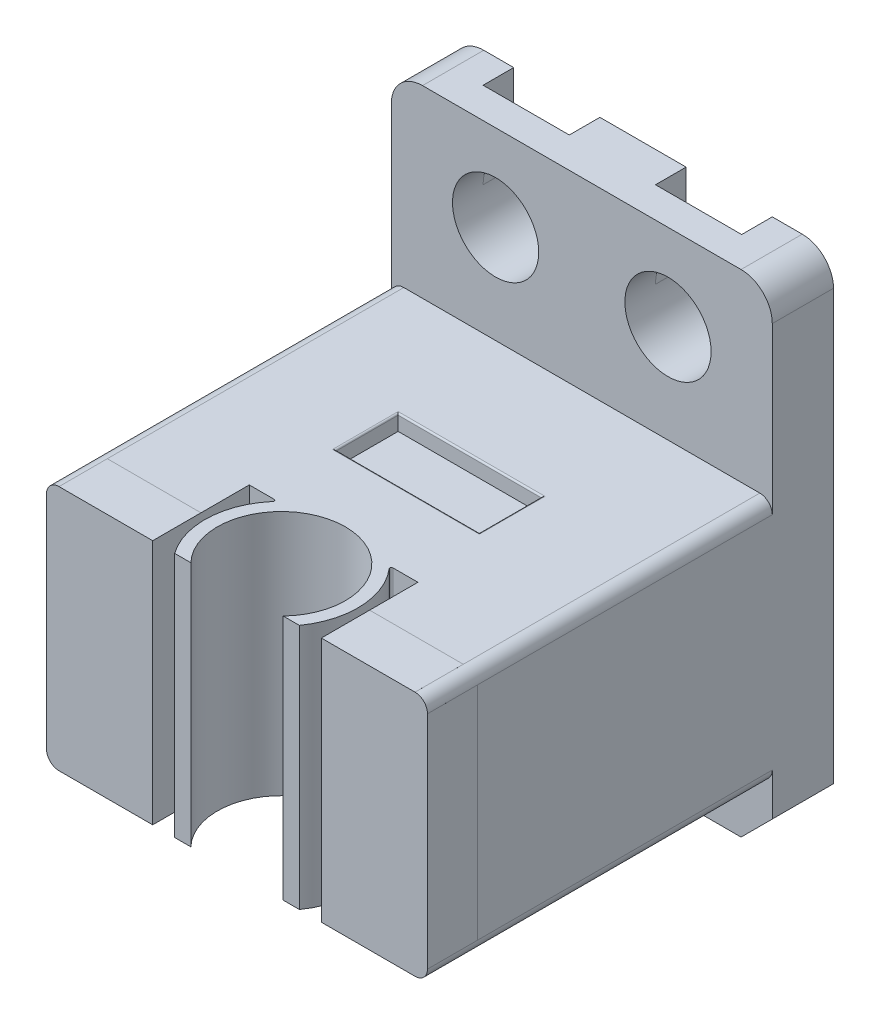
SolidWorks part; units mm, degrees
ref_plane "Front Plane" through (0, 0, 0) normal (0, 0, 1) x (1, 0, 0)
ref_plane "Top Plane" through (0, 0, 0) normal (0, 1, 0) x (1, 0, 0)
ref_plane "Right Plane" through (0, 0, 0) normal (1, 0, 0) x (0, 0, -1)
sketch "Sketch2" plane through (0, 0, 0) normal (0, 0, 1) x (1, 0, 0)
  line L0 (-5.2578, 6.4897) -> (-1.4809, 6.4897) construction
  line L1 (-6.477, 9.9949) -> (6.477, 9.9949)
  line L2 (-7.747, 8.7249) -> (-7.747, -9.9949)
  line L3 (-7.747, -9.9949) -> (7.747, -9.9949)
  line L4 (7.747, 8.7249) -> (7.747, -9.9949)
  line L5 (-7.747, 9.9949) -> (7.747, -9.9949) construction
  line L6 (-7.747, -9.9949) -> (7.747, 9.9949) construction
  line L7 (0, -9.9949) -> (0, 19.523) construction
  circle A0 centre (-3.5052, 6.4897) radius 1.7526
  circle A1 centre (3.5052, 6.4897) radius 1.7526
  arc A2 (6.477, 9.9949) -> (7.747, 8.7249) centre (6.477, 8.7249) cw
  arc A3 (-6.477, 9.9949) -> (-7.747, 8.7249) centre (-6.477, 8.7249) ccw
  point P0 (0, 0)
  dimension "D3" = 7.0104
  dimension "D4" = 3.5052
  dimension "D5" = 3.5052
  dimension "D6" = 3.5052
  dimension "D8" = 1.27
  dimension "D1" = 15.494
  dimension "D2" = 19.9898
  dimension "D7" = 3.5052
extrude "Boss-Extrude1" add sketch "Sketch2" along normal blind 2.4892
sketch "Sketch3" plane through (0, 0, 2.4892) normal (0, 0, 1) x (1, 0, 0)
  line L0 (7.747, -9.9949) -> (7.747, 8.7249) construction
  line L1 (0, 16.793) -> (0, -17.5216) construction
  line L2 (-13.8424, -2.5019) -> (21.1306, -2.5019) construction
  line L4 (-5.2578, 6.4897) -> (11.8832, 6.4897) construction
  line L5 (-7.239, 2.5019) -> (7.239, 2.5019)
  line L6 (-7.747, 1.9939) -> (-7.747, -6.9977)
  line L7 (-7.239, -7.5057) -> (7.239, -7.5057)
  line L8 (7.747, 1.9939) -> (7.747, -6.9977)
  line L9 (-7.747, 2.5019) -> (7.747, -7.5057) construction
  line L10 (-7.747, -7.5057) -> (7.747, 2.5019) construction
  circle A0 centre (-3.5052, 6.4897) radius 1.7526 construction
  arc A1 (7.239, 2.5019) -> (7.747, 1.9939) centre (7.239, 1.9939) cw
  arc A2 (7.239, -7.5057) -> (7.747, -6.9977) centre (7.239, -6.9977) ccw
  arc A3 (-7.747, -6.9977) -> (-7.239, -7.5057) centre (-7.239, -6.9977) ccw
  arc A4 (-7.239, 2.5019) -> (-7.747, 1.9939) centre (-7.239, 1.9939) ccw
  point P0 (0, -2.5019)
  dimension "D3" = 0.508
  dimension "D1" = 8.9916
  dimension "D2" = 10.0076
extrude "Boss-Extrude2" add sketch "Sketch3" along normal blind 14.0208
sketch "Sketch4" plane through (0, -7.5057, 0) normal (0, -1, 0) x (1, 0, 0)
  line L0 (0, -1.7528) -> (0, 17.6382) construction
  line L1 (-9.4019, 8.3058) -> (11.8673, 8.3058) construction
  line L2 (-3.429, 12.5824) -> (-2.413, 12.5824)
  line L3 (-19.205, 14.7066) -> (19.1548, 14.7066) construction
  line L4 (-7.747, 0) -> (7.747, 0) construction
  line L5 (-3.429, 16.51) -> (-2.5356, 16.51)
  line L10 (-7.239, 16.51) -> (7.239, 16.51) construction
  line L11 (-3.429, 16.51) -> (-3.429, 12.5824)
  line L12 (3.429, 16.51) -> (3.429, 12.5824)
  line L13 (3.429, 16.51) -> (2.5356, 16.51)
  line L14 (3.429, 12.5824) -> (2.413, 12.5824)
  circle A0 centre (0, 14.7066) radius 2.6035
  arc A1 (2.3656, 12.6853) -> (2.5356, 16.51) centre (0, 14.7066) ccw
  arc A2 (-2.413, 12.5824) -> (-2.3656, 12.6853) centre (-2.413, 12.6448) ccw
  arc A3 (2.413, 12.5824) -> (2.3656, 12.6853) centre (2.413, 12.6448) cw
  arc A4 (-2.5356, 16.51) -> (-2.3656, 12.6853) centre (0, 14.7066) ccw
  point P12 (0, 8.3058)
  dimension "D3" = 5.207
  dimension "D4" = 0.508
  dimension "D5" = 0.0624
  dimension "D1" = 14.7066
  dimension "D2" = 8.3058
  dimension "D6" = 6.858
  dimension "D7" = 1.016
extrude "Cut-Extrude3" cut sketch "Sketch4" against normal through all
sketch "Sketch5" plane through (0, 2.5019, 0) normal (0, 1, 0) x (1, 0, 0)
  line L0 (10.9012, -8.3058) -> (-14.0254, -8.3058) construction
  line L1 (0, 0) -> (0, -20.817) construction
  line L2 (6.477, 0) -> (-6.477, 0) construction
  line L3 (3.429, -12.5824) -> (3.429, -16.51) construction
  line L4 (2.921, -9.5758) -> (-2.921, -9.5758)
  line L5 (2.921, -9.5758) -> (2.921, -7.0358)
  line L6 (2.921, -7.0358) -> (-2.921, -7.0358)
  line L7 (-2.921, -9.5758) -> (-2.921, -7.0358)
  line L8 (2.921, -9.5758) -> (-2.921, -7.0358) construction
  line L9 (2.921, -7.0358) -> (-2.921, -9.5758) construction
  point P8 (0, -8.3058)
  dimension "D1" = 8.3058
  dimension "D2" = 2.54
  dimension "D3" = 0.508
extrude "Cut-Extrude4" cut sketch "Sketch5" against normal blind 0.635
fillet "Fillet1" radius 0.0648 4 edges at (-2.921, 2.5019, 8.3058) (0, 2.5019, 7.0358) (2.921, 2.5019, 8.3058) (0, 2.5019, 9.5758)
sketch "Sketch6" plane through (0, -9.9949, 0) normal (0, -1, 0) x (1, 0, 0)
  line L0 (-10.0705, 5.9776) -> (12.9955, 5.9776) construction
  line L1 (0, -2.2125) -> (0, 17.7614) construction
  line L3 (-7.747, 0) -> (7.747, 0) construction
  circle A0 centre (0, 2.9972) radius 2.6035
  dimension "D1" = 5.207
  dimension "D2" = 2.9972
extrude "Boss-Extrude3" add sketch "Sketch6" against normal up to next and the other way blind 1.27
sketch "Sketch7" plane through (0, -11.2649, 0) normal (0, -1, 0) x (1, 0, 0)
  circle A0 centre (0, 2.9972) radius 2.3495
  circle A1 centre (0, 2.9972) radius 2.6035 construction
  dimension "D1" = 0.254
extrude "Boss-Extrude4" add sketch "Sketch7" along normal blind 0.7366
fillet "Fillet2" radius 0.127 1 edges at (0, -11.2649, 0.6477)
sketch "Sketch8" plane through (0, 9.9949, 0) normal (0, 1, 0) x (1, 0, 0)
  line L0 (9.0247, -1.2446) -> (-10.9399, -1.2446) construction
  line L1 (6.477, -2.4892) -> (-6.477, -2.4892) construction
  line L2 (6.477, 0) -> (-6.477, 0) construction
  line L3 (0, -5.7739) -> (0, 1.6257) construction
  line L4 (5.2578, 0) -> (1.7526, 0)
  line L5 (5.2578, 0) -> (5.2578, -1.2446)
  line L6 (5.2578, -1.2446) -> (1.7526, -1.2446)
  line L7 (1.7526, 0) -> (1.7526, -1.2446)
  line L8 (-1.7526, 0) -> (-5.2578, 0)
  line L9 (-1.7526, 0) -> (-1.7526, -1.2446)
  line L10 (-1.7526, -1.2446) -> (-5.2578, -1.2446)
  line L11 (-5.2578, 0) -> (-5.2578, -1.2446)
  line L12 (3.5052, -1.2446) -> (3.5052, 0) construction
  line L13 (-3.5052, -1.2446) -> (-3.5052, 0) construction
  dimension "D1" = 3.5052
  dimension "D2" = 3.5052
  dimension "D3" = 7.0104
  dimension "D4" = 3.5052
extrude "Cut-Extrude5" cut sketch "Sketch8" against normal blind 3.5052
chamfer "Chamfer1" distance 1.27 angle 45 2 edges at (-7.747, -9.9949, 1.2446) (7.747, -9.9949, 1.2446)
sketch "Sketch11" plane through (0, 2.5019, 0) normal (0, 1, 0) x (1, 0, 0)
  line L0 (3.429, -12.5824) -> (3.429, -16.51) construction
  line L1 (7.239, -16.51) -> (3.429, -16.51)
  line L2 (7.239, -16.51) -> (7.239, -14.5462)
  line L3 (7.239, -14.5462) -> (3.429, -14.5462)
  line L4 (3.429, -16.51) -> (3.429, -14.5462)
  line L5 (-7.239, -16.51) -> (-7.239, -2.4892) construction
  line L6 (-3.429, -16.51) -> (-7.239, -16.51)
  line L7 (-3.429, -16.51) -> (-3.429, -14.5462)
  line L8 (-3.429, -14.5462) -> (-7.239, -14.5462)
  line L9 (-7.239, -16.51) -> (-7.239, -14.5462)
  dimension "D1" = 0
extrude "Boss-Extrude5" add sketch "Sketch11" along normal blind 0.0003
sketch "Sketch12" plane through (7.747, 0, 0) normal (1, 0, 0) x (0, 0, -1)
  line L0 (-16.51, -6.9977) -> (-2.4892, -6.9977) construction
  line L1 (-16.51, 1.9939) -> (-14.478, 1.9939)
  line L2 (-16.51, 1.9939) -> (-16.51, -6.9977)
  line L3 (-16.51, -6.9977) -> (-14.478, -6.9977)
  line L4 (-14.478, 1.9939) -> (-14.478, -6.9977)
  dimension "D1" = 2.032
extrude "Boss-Extrude6" add sketch "Sketch12" along normal blind 0.0003
sketch "Sketch14" plane through (0, -7.5057, 0) normal (0, -1, 0) x (1, 0, 0)
  line L0 (7.239, 16.51) -> (7.239, 2.4892) construction
  line L1 (-7.239, 16.51) -> (-3.429, 16.51)
  line L2 (-7.239, 16.51) -> (-7.239, 14.5462)
  line L3 (-7.239, 14.5462) -> (-3.429, 14.5462)
  line L4 (-3.429, 16.51) -> (-3.429, 14.5462)
  line L5 (3.429, 16.51) -> (7.239, 16.51)
  line L6 (3.429, 16.51) -> (3.429, 14.478)
  line L7 (3.429, 14.478) -> (7.239, 14.478)
  line L8 (7.239, 16.51) -> (7.239, 14.478)
  dimension "D1" = 2.032
extrude "Boss-Extrude7" add sketch "Sketch14" along normal blind 0.0003
sketch "Sketch15" plane through (-7.747, 0, 0) normal (-1, 0, 0) x (0, 0, 1)
  line L0 (16.51, -6.9977) -> (2.4892, -6.9977) construction
  line L1 (16.51, 1.9939) -> (14.478, 1.9939)
  line L2 (16.51, 1.9939) -> (16.51, -6.9977)
  line L3 (16.51, -6.9977) -> (14.478, -6.9977)
  line L4 (14.478, 1.9939) -> (14.478, -6.9977)
  dimension "D1" = 2.032
extrude "Boss-Extrude8" add sketch "Sketch15" along normal blind 0.0003
sketch "Sketch19" plane through (-7.747, 0, 0) normal (-1, 0, 0) x (0, 0, 1)
  text T0 "Panasonic" font "Century Gothic" height in points 6
extrude "Boss-Extrude9" add sketch "Sketch19" along normal blind 0.0003
